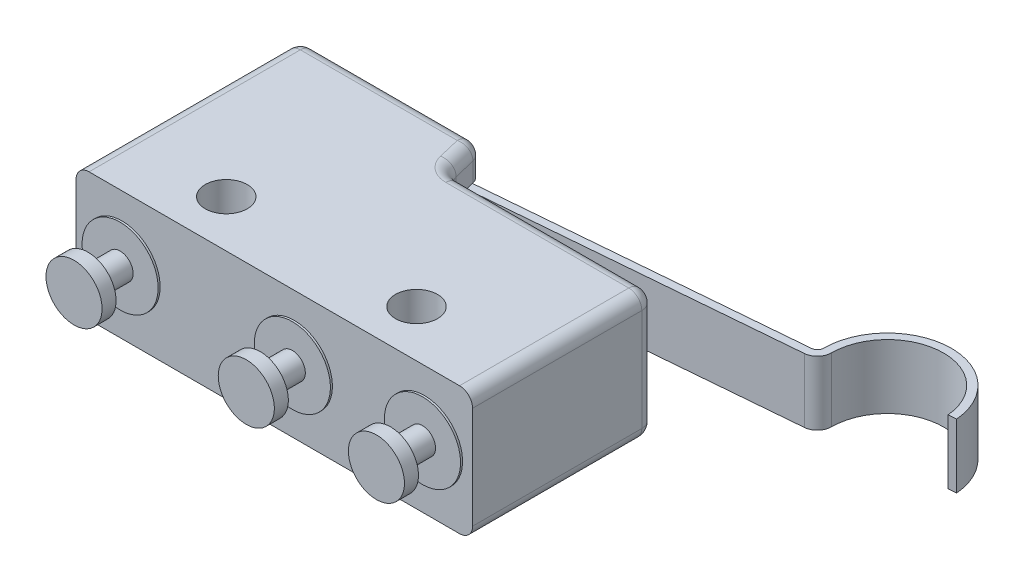
SolidWorks part; units mm, degrees
ref_plane "Front Plane" through (0, 0, 0) normal (0, 0, 1) x (1, 0, 0)
ref_plane "Top Plane" through (0, 0, 0) normal (0, 1, 0) x (1, 0, 0)
ref_plane "Right Plane" through (0, 0, 0) normal (1, 0, 0) x (0, 0, -1)
sketch "Sketch2" plane through (0, 0, 0) normal (0, 1, 0) x (1, 0, 0)
  line L1 (0, 0) -> (19.8, 0)
  line L2 (0, 0) -> (0, 11.2)
  line L3 (0, 11.2) -> (9, 11.2)
  line L4 (19.8, 0) -> (19.8, 9.1)
  line L6 (9, 11.2) -> (9.5, 9.1)
  line L7 (9.5, 9.1) -> (19.8, 9.1)
  dimension "D1" = 11.2
  dimension "D2" = 19.8
  dimension "D3" = 9
  dimension "D4" = 9.5
  dimension "D5" = 9.1
extrude "Boss-Extrude1" add sketch "Sketch2" along normal mid plane 6.4
sketch "Sketch3" plane through (0, 3.2, 0) normal (0, 1, 0) x (1, 0, 0)
  line L0 (19.8, 0) -> (19.8, 9.1) construction
  line L1 (0, 11.2) -> (0, 0) construction
  line L2 (0, 0) -> (19.8, 0) construction
  line L3 (14.65, 0) -> (14.65, 1.3) construction
  line L4 (14.65, 1.3) -> (15.7, 2.35) construction
  line L5 (15.7, 2.35) -> (19.8, 2.35) construction
  circle A0 centre (5.15, 2.35) radius 1.05
  circle A1 centre (14.65, 2.35) radius 1.05
  dimension "D1" = 2.1
  dimension "D5" = 2.1
  dimension "D2" = 9.5
  dimension "D3" = 5.15
  dimension "D4" = 5.15
  dimension "D6" = 2.35
  dimension "D7" = 4.1
  dimension "D8" = 1.3
extrude "Cut-Extrude1" cut sketch "Sketch3" against normal blind 16.4
sketch "Sketch4" plane through (0, 0, 0) normal (0, 1, 0) x (1, 0, 0)
  line L0 (1.2922, 10.0017) -> (25.0259, 12.0278)
  line L1 (0, 11.2) -> (0, 0) construction
  line L2 (0, 0) -> (28.2143, 0) construction
  line L3 (28.2143, 0) -> (28.2143, 15.5) construction
  line L4 (28.2143, 15.5) -> (37.8779, 15.5) construction
  arc A0 (31.4027, 12.5722) -> (25.0259, 12.0278) centre (28.2143, 12.3) ccw
  dimension "D1" = 3.2
  dimension "D2" = 30.22
  dimension "D3" = 31.4027
  dimension "D4" = 15.5
extrude "Extrude-Thin1" add sketch "Sketch4" along normal mid plane 3.2 thin thin type one direction reverse wall 0.4
fillet "Fillet1" radius 0.65 14 edges at (0, 0, -11.2) (0, 3.2, -5.6) (0, -3.2, -5.6) (9.25, -3.2, -10.15) (9, 0, -11.2) (14.65, -3.2, -9.1) (19.8, -3.2, -4.55) (9.5, 0, -9.1) (19.8, 0, -9.1) (19.8, 3.2, -4.55) (14.65, 3.2, -9.1) (9.25, 3.2, -10.15) (4.5, -3.2, -11.2) (4.5, 3.2, -11.2)
sketch "Sketch5" plane through (-0.8383, 0, -9.8198) normal (-0.0851, 0, -0.9964) x (-0.9964, 0, 0.0851)
  line L0 (-25.9583, 1.6) -> (-10.0006, 1.6) construction
  line L1 (-11.5805, 1.6) -> (1.9987, 1.6)
  line L2 (-11.5805, 1.6) -> (-11.5805, -1.6)
  line L3 (-11.5805, -1.6) -> (1.9987, -1.6)
  line L4 (1.9987, 1.6) -> (1.9987, -1.6)
extrude "Cut-Extrude2" cut sketch "Sketch5" along normal blind 16.4
fillet "Fillet2" radius 0.3 1 edges at (25.0259, 0, -12.0278)
fillet "Fillet3" radius 0.7 1 edges at (25.4871, 0, -11.6657)
sketch "Sketch6" plane through (0, 0, 0) normal (0, 1, 0) x (1, 0, 0)
  line L0 (2.3, 0.659) -> (2.3, -2.4)
  line L1 (2.3, -2.4) -> (3.7, -2.4)
  line L2 (3.7, -2.4) -> (3.7, -1.7)
  line L3 (3.7, -1.7) -> (2.95, -1.7)
  line L4 (2.95, -1.7) -> (2.95, -0.1)
  line L5 (2.95, -0.1) -> (4.2, -0.1)
  line L6 (0.65, 0) -> (19.15, 0) construction
  line L7 (0, 0) -> (0, 10.55) construction
  line L8 (4.2, -0.1) -> (4.2, 0.659)
  line L9 (4.2, 0.659) -> (2.3, 0.659)
  dimension "D1" = 1.4
  dimension "D2" = 0.65
  dimension "D3" = 2.4
  dimension "D4" = 0.7
  dimension "D5" = 2.3
  dimension "D6" = 1.9
  dimension "D7" = 0.1
revolve "Revolve1" add sketch "Sketch6" angle 360 about L0
pattern_linear "LPattern1" count 2 spacing 15.1 along (1, 0, 0) of "Revolve1"
pattern_linear "LPattern2" count 2 spacing 8.6 along (1, 0, 0) of "Revolve1"
ref_plane "ON level" through (0, 0, -13) normal (0, 0, 1) x (1, 0, 0)
ref_plane "Plane2" through (28, 0, 0) normal (1, 0, 0) x (0, 0, -1)
ref_axis "push direction" through (28, 0, -16.395) along (0, 0, 1)
